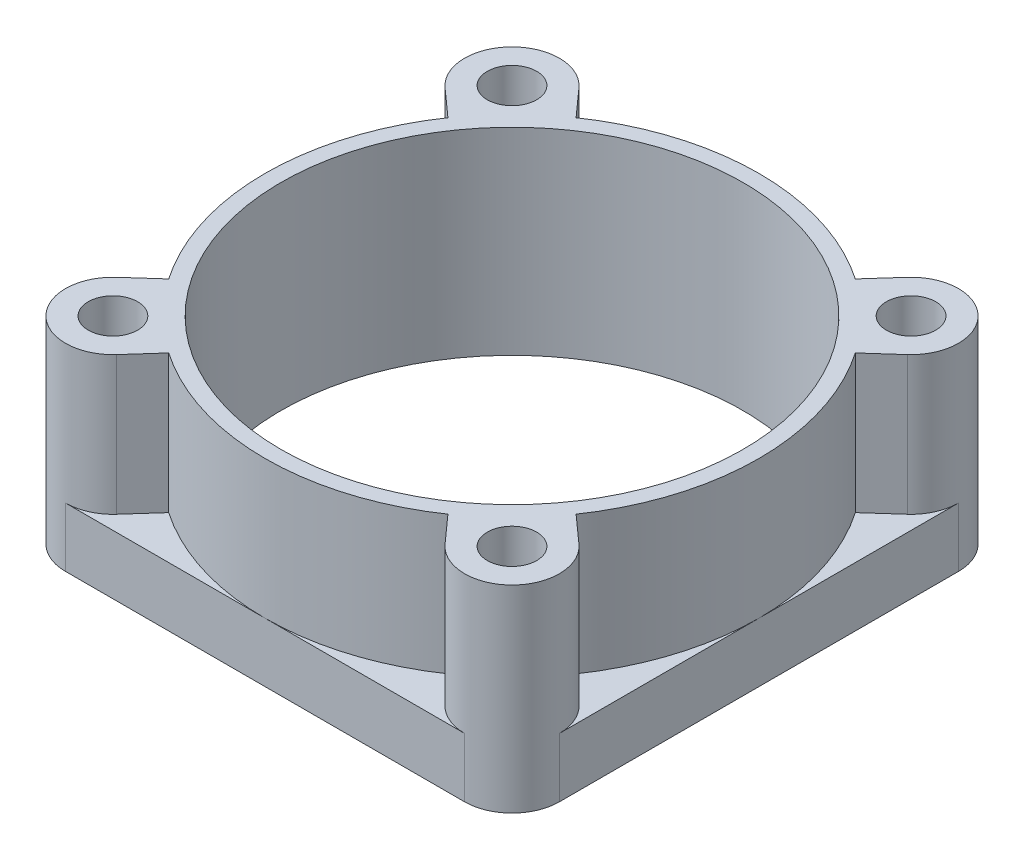
SolidWorks part; units mm, degrees
material "6061 合金"
ref_plane "前视基准面" through (0, 0, 0) normal (0, 0, 1) x (1, 0, 0)
ref_plane "上视基准面" through (0, 0, 0) normal (0, 1, 0) x (1, 0, 0)
ref_plane "右视基准面" through (0, 0, 0) normal (1, 0, 0) x (0, 0, -1)
other "Configuration Table"
sketch "草图1" plane through (0, 0, 0) normal (0, 1, 0) x (1, 0, 0)
  line L1 (-10.1, -12.5) -> (10.1, -12.5)
  line L2 (-12.5, -10.1) -> (-12.5, 10.1)
  line L3 (-10.1, 12.5) -> (10.1, 12.5)
  line L4 (12.5, -10.1) -> (12.5, 10.1)
  line L5 (-12.5, -12.5) -> (12.5, 12.5) construction
  line L6 (-12.5, 12.5) -> (12.5, -12.5) construction
  circle A0 centre (0, 0) radius 12.5 construction
  circle A1 centre (0, 0) radius 11.7
  arc A2 (-10.1, -12.5) -> (-12.5, -10.1) centre (-10.1, -10.1) cw
  arc A3 (10.1, -12.5) -> (12.5, -10.1) centre (10.1, -10.1) ccw
  arc A4 (10.1, 12.5) -> (12.5, 10.1) centre (10.1, 10.1) cw
  arc A5 (-12.5, 10.1) -> (-10.1, 12.5) centre (-10.1, 10.1) cw
  point P0 (0, 0)
  dimension "D3" = 2.4
  dimension "D1" = 25
  dimension "D2" = 25
extrude "凸台-拉伸1" add sketch "草图1" along normal blind 3
sketch "草图2" plane through (0, 3, 0) normal (0, 1, 0) x (1, 0, 0)
  line L0 (-10.1, -12.5) -> (10.1, -12.5) construction
  line L1 (12.5, -10.1) -> (12.5, 10.1) construction
  line L2 (-12.5, 10.1) -> (-12.5, -10.1) construction
  line L3 (10.1, 12.5) -> (-10.1, 12.5) construction
  line L4 (-10.1, -12.5) -> (10.1, -12.5)
  line L5 (12.5, -10.1) -> (12.5, 10.1)
  line L6 (-12.5, 10.1) -> (-12.5, -10.1)
  line L7 (10.1, 12.5) -> (-10.1, 12.5)
  line L8 (-8.3118, 11.7008) -> (-7.0672, 10.3104)
  line L9 (-11.7008, 8.3118) -> (-10.3104, 7.0672)
  line L10 (8.3118, 11.7008) -> (7.0672, 10.3104)
  line L11 (11.7008, 8.3118) -> (10.3104, 7.0672)
  line L12 (11.7008, -8.3118) -> (10.3104, -7.0672)
  line L13 (8.3118, -11.7008) -> (7.0672, -10.3104)
  line L14 (-8.3118, -11.7008) -> (-7.0672, -10.3104)
  line L15 (-11.7008, -8.3118) -> (-10.3104, -7.0672)
  arc A0 (-12.5, -10.1) -> (-10.1, -12.5) centre (-10.1, -10.1) ccw construction
  arc A1 (10.1, -12.5) -> (12.5, -10.1) centre (10.1, -10.1) ccw construction
  arc A2 (12.5, 10.1) -> (10.1, 12.5) centre (10.1, 10.1) ccw construction
  circle A3 centre (0, 0) radius 11.7 construction
  arc A4 (-10.1, 12.5) -> (-12.5, 10.1) centre (-10.1, 10.1) ccw construction
  arc A5 (-12.5, -10.1) -> (-10.1, -12.5) centre (-10.1, -10.1) ccw
  arc A6 (10.1, -12.5) -> (12.5, -10.1) centre (10.1, -10.1) ccw
  arc A7 (12.5, 10.1) -> (10.1, 12.5) centre (10.1, 10.1) ccw
  circle A8 centre (0, 0) radius 11.7
  arc A9 (-10.1, 12.5) -> (-12.5, 10.1) centre (-10.1, 10.1) ccw
  arc A10 (-10.3104, 7.0672) -> (-10.3104, -7.0672) centre (0, 0) ccw
  arc A11 (-10.1, 12.5) -> (-8.3118, 11.7008) centre (-10.1, 10.1) cw
  arc A12 (-12.5, 10.1) -> (-11.7008, 8.3118) centre (-10.1, 10.1) ccw
  circle A13 centre (0, 0) radius 12.5 construction
  circle A14 centre (-10.1, 10.1) radius 1.25
  arc A15 (12.5, 10.1) -> (10.1, 12.5) centre (10.1, 10.1) ccw
  arc A16 (12.5, 10.1) -> (11.7008, 8.3118) centre (10.1, 10.1) cw
  arc A17 (10.1, 12.5) -> (8.3118, 11.7008) centre (10.1, 10.1) ccw
  circle A18 centre (10.1, 10.1) radius 1.25
  arc A19 (10.1, -12.5) -> (12.5, -10.1) centre (10.1, -10.1) ccw
  arc A20 (10.1, -12.5) -> (8.3118, -11.7008) centre (10.1, -10.1) cw
  arc A21 (12.5, -10.1) -> (11.7008, -8.3118) centre (10.1, -10.1) ccw
  circle A22 centre (10.1, -10.1) radius 1.25
  arc A23 (-12.5, -10.1) -> (-10.1, -12.5) centre (-10.1, -10.1) ccw
  arc A24 (-12.5, -10.1) -> (-11.7008, -8.3118) centre (-10.1, -10.1) cw
  arc A25 (-10.1, -12.5) -> (-8.3118, -11.7008) centre (-10.1, -10.1) ccw
  circle A26 centre (-10.1, -10.1) radius 1.25
  arc A27 (7.0672, 10.3104) -> (-7.0672, 10.3104) centre (0, 0) ccw
  arc A28 (10.3104, -7.0672) -> (10.3104, 7.0672) centre (0, 0) ccw
  arc A29 (-7.0672, -10.3104) -> (7.0672, -10.3104) centre (0, 0) ccw
  point P49 (0, 0)
  arc M1 (-12.5, -10.1) -> (-10.1, -12.5) centre (-10.1, -10.1) ccw
  arc M3 (10.1, -12.5) -> (12.5, -10.1) centre (10.1, -10.1) ccw
  arc M5 (12.5, 10.1) -> (10.1, 12.5) centre (10.1, 10.1) ccw
  arc M7 (-10.1, 12.5) -> (-12.5, 10.1) centre (-10.1, 10.1) ccw
  circle M9 centre (0, 0) radius 11.7
  dimension "D1" = 4
  dimension "D2" = 2.5
extrude "凸台-拉伸2" add sketch "草图2" along normal blind 7 contours A29 L13 A20 A21 L12 A28 L11 A16 A17 L10 A27 L8 A11 A12 L9 A10 L15 A24 A25 L14 A26 A22 A18 A14 M3 M5 M7 M1 M9 region at (-11.5471, 3, 11.5471)
extrude "切除-拉伸1" cut sketch "草图2<3>" against normal through all contours A22 | A26 | A14 | A18
sketch "草图2<3>" plane through (0, 3, 0) normal (0, 1, 0) x (1, 0, 0) same geometry as "草图2"
